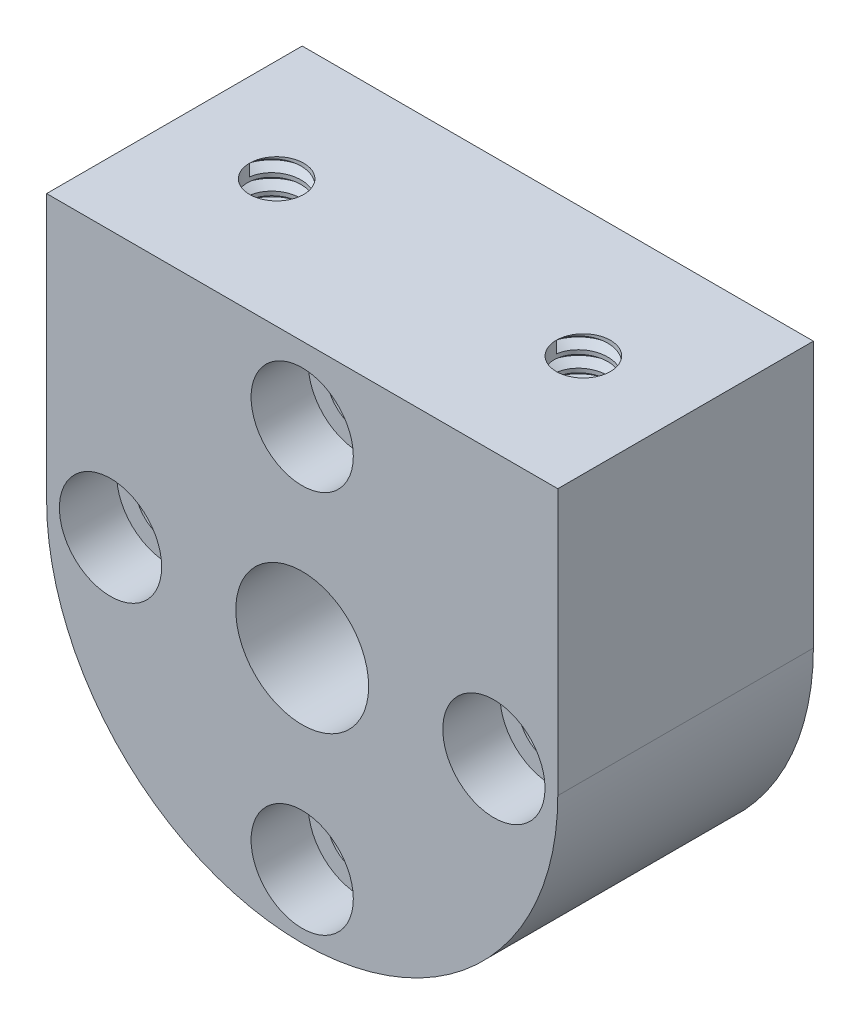
SolidWorks part; units mm, degrees
ref_plane "Front Plane" through (0, 0, 0) normal (0, 0, 1) x (1, 0, 0)
ref_plane "Top Plane" through (0, 0, 0) normal (0, 1, 0) x (1, 0, 0)
ref_plane "Right Plane" through (0, 0, 0) normal (1, 0, 0) x (0, 0, -1)
sketch "Sketch1" plane through (0, 0, 0) normal (0, 0, 1) x (1, 0, 0)
  line L3 (-12.7, 0) -> (-12.7, 13.208)
  line L4 (-12.7, 13.208) -> (12.7, 13.208)
  line L5 (12.7, 0) -> (12.7, 13.208)
  arc A0 (-12.7, 0) -> (12.7, 0) centre (0, 0) ccw
  point P5 (0, 0)
  dimension "D1" = 25.4
  dimension "D2" = 13.208
extrude "Boss-Extrude1" add sketch "Sketch1" along normal blind 12.7
sketch "Sketch2" plane through (0, 0, 12.7) normal (0, 0, 1) x (1, 0, 0)
  circle A0 centre (0, 0) radius 3.302
  dimension "D1" = 6.604
extrude "Cut-Extrude1" cut sketch "Sketch2" against normal blind 12.7
hole_wizard "CBORE for #4 Socket Head Cap Screw1" positions "Sketch3" profile "Sketch5" counterbore size "#4" standard "ANSI Inch" end condition through all
sketch "Sketch3" plane through (0, 0, 12.7) normal (0, 0, 1) x (1, 0, 0)
  circle A0 centre (0, 0) radius 9.525 construction
  point P5 (0, 9.525)
  point P7 (9.525, 0)
  point P9 (0, -9.525)
  point P11 (-9.525, 0)
  dimension "D1" = 19.05
sketch "Sketch5" plane through (-9.525, 0, 12.7) normal (1, 0, 0) x (0, -1, 0)
  line L0 (0, 0) -> (0, 12.7)
  line L1 (0, 12.7) -> (1.6319, 12.7)
  line L3 (1.6319, 12.7) -> (1.632, 2.8448)
  line L4 (1.632, 2.8448) -> (2.54, 2.8448)
  line L5 (2.54, 2.8448) -> (2.54, 0)
  line L7 (2.54, 0) -> (0, 0)
  line L11 (0, -6.35) -> (0, 107.95) construction
  dimension "Thru Hole Dia." = 3.2639
  dimension "Thru Hole Depth" = 12.7
  dimension "C'Bore Dia." = 5.08
  dimension "C'Bore Depth" = 2.8448
sketch "Sketch9" plane through (0, 13.208, 0) normal (0, 1, 0) x (1, 0, 0)
  line L0 (0, 0) -> (0, -12.7) construction
  line L1 (12.7, -12.7) -> (-12.7, -12.7) construction
  line L2 (-7.62, -6.35) -> (7.62, -6.35) construction
  circle A0 centre (-7.62, -6.35) radius 1.3462
  circle A1 centre (7.62, -6.35) radius 1.3462
  point P8 (0, -6.35)
  dimension "D2" = 2.6924
  dimension "D1" = 15.24
extrude "Cut-Extrude3" cut sketch "Sketch9" against normal blind 8.89
thread "Thread1" pitch 0.7937 method cut profile "Thread Profile1" start angle 0, offset 0, length 0, pitch 0.7937, diameter 2.6924
ref_plane "Plane2" through (-8.9662, 13.208, 6.35) normal (0, 0, 1) x (-1, 0, 0)
sketch "Thread Profile1" plane through (-8.9662, 13.208, 6.35) normal (0, 0, 1) x (-1, 0, 0)
  line L0 (0, 0) -> (0, 0.7937) construction
  line L1 (0, 0) -> (0.4296, 0.248)
  line L2 (0.4296, 0.248) -> (0.4296, 0.3473)
  line L3 (0.4296, 0.3473) -> (0, 0.5953)
  line L4 (0.4296, 0.2977) -> (0, 0.2977) construction
  line L11 (0, 0) -> (0, 0.5953)
  point P2 (0, 0)
  dimension "Pitch" = 0.7937
  dimension "Profile_Angle" = 60
  dimension "Profile_Land" = 0.0992
  dimension "Profile_Height" = 0.4296
thread "Thread2" pitch 0.7937 method cut profile "Thread Profile2" start angle 0, offset 0, length 0, pitch 0.7937, diameter 2.6924
ref_plane "Plane3" through (6.2738, 13.208, 6.35) normal (0, 0, 1) x (-1, 0, 0)
sketch "Thread Profile2" plane through (6.2738, 13.208, 6.35) normal (0, 0, 1) x (-1, 0, 0)
  line L0 (0, 0) -> (0, 0.7937) construction
  line L1 (0, 0) -> (0.4296, 0.248)
  line L2 (0.4296, 0.248) -> (0.4296, 0.3473)
  line L3 (0.4296, 0.3473) -> (0, 0.5953)
  line L4 (0.4296, 0.2977) -> (0, 0.2977) construction
  line L11 (0, 0) -> (0, 0.5953)
  point P2 (0, 0)
  dimension "Pitch" = 0.7937
  dimension "Profile_Angle" = 60
  dimension "Profile_Land" = 0.0992
  dimension "Profile_Height" = 0.4296
